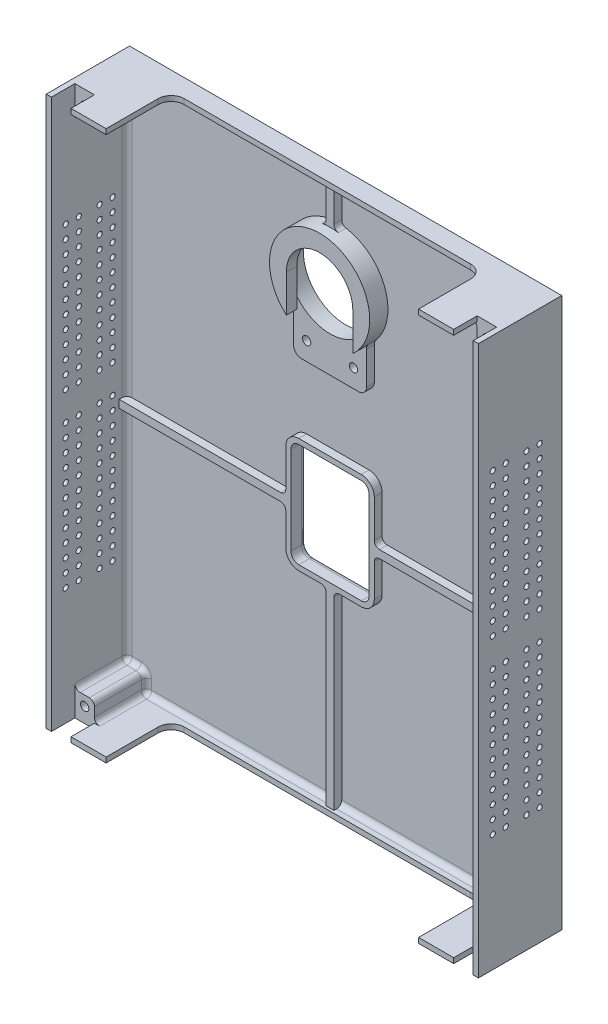
SolidWorks part; units mm, degrees
ref_plane "Front Plane" through (0, 0, 0) normal (0, 0, 1) x (1, 0, 0)
ref_plane "Top Plane" through (0, 0, 0) normal (0, 1, 0) x (1, 0, 0)
ref_plane "Right Plane" through (0, 0, 0) normal (1, 0, 0) x (0, 0, -1)
ref_plane "Plane1" through (0, 0, -1) normal (0, 0, 1) x (1, 0, 0)
sketch "Sketch5" plane through (0, 0, -1) normal (0, 0, 1) x (1, 0, 0)
  line L0 (100, 83.2573) -> (100, -169.2647) construction
  line L2 (17, 83.2573) -> (17, -127.7573)
  line L3 (17, -127.7573) -> (183, -127.7573)
  line L4 (183, 83.2573) -> (183, -127.7573)
  line L5 (17, 83.2573) -> (183, 83.2573)
  circle A0 centre (100, 48.2573) radius 16.25
  point P17 (45, 83.2573)
  dimension "D1" = 166
  dimension "D2" = 83
extrude "Boss-Extrude5" add sketch "Sketch5" along normal blind 3
sketch "Sketch6" plane through (0, 0, 2) normal (0, 0, 1) x (1, 0, 0)
  line L0 (116.25, 48.2573) -> (83.75, 48.2573) construction
  line L2 (86, 35.0451) -> (86, 18.2573)
  line L3 (86, 18.2573) -> (114, 18.2573)
  line L4 (114, 35.0451) -> (114, 18.2573)
  line L5 (100, 48.2573) -> (100, 52.872) construction
  circle A1 centre (100, 48.2573) radius 16.25
  arc A2 (114, 35.0451) -> (86, 35.0451) centre (100, 48.2573) ccw
  circle A6 centre (100, 48.2573) radius 16.25 construction
extrude "Boss-Extrude6" add sketch "Sketch6" along normal blind 3
sketch "Sketch7" plane through (0, 0, 5) normal (0, 0, 1) x (1, 0, 0)
  line L0 (112.75, 33.8351) -> (112.75, 48.2573)
  line L2 (87.25, 48.2573) -> (87.25, 33.8351)
  line L3 (100, 64.5073) -> (100, 48.2573) construction
  line L4 (100, 48.2573) -> (116.25, 48.2573) construction
  arc A8 (112.75, 33.8351) -> (87.25, 33.8351) centre (100, 48.2573) ccw
  circle A9 centre (100, 48.2573) radius 19.25 construction
  circle A10 centre (100, 48.2573) radius 16.25 construction
  circle A12 centre (100, 48.2573) radius 12.75
  arc A13 (112.75, 48.2573) -> (87.25, 48.2573) centre (100, 48.2573) ccw
  dimension "D1" = 1
extrude "Boss-Extrude7" add sketch "Sketch7" along normal blind 4
sketch "Sketch8" plane through (0, 0, 2) normal (0, 0, 1) x (1, 0, 0)
  line L4 (17, -127.7573) -> (183, -127.7573)
  line L5 (183, -127.7573) -> (183, 83.2573)
  line L6 (183, 83.2573) -> (17, 83.2573)
  line L7 (17, 83.2573) -> (17, -127.7573)
  line L8 (17, -127.7573) -> (183, -127.7573)
  line L9 (183, -127.7573) -> (183, 83.2573)
  line L10 (183, 83.2573) -> (17, 83.2573)
  line L11 (17, 83.2573) -> (17, -127.7573)
  line L12 (19, -125.7573) -> (181, -125.7573)
  line L13 (181, -125.7573) -> (181, 81.2573)
  line L14 (181, 81.2573) -> (19, 81.2573)
  line L15 (19, 81.2573) -> (19, -125.7573)
  dimension "D1" = 0
  dimension "D2" = 2
extrude "Boss-Extrude8" add sketch "Sketch8" along normal blind 29
fillet "Fillet2" radius 3 4 edges at (114, 18.2573, 3.5) (114, 35.0451, 3.5) (86, 18.2573, 3.5) (86, 35.0451, 3.5)
sketch "Sketch9" plane through (0, 0, 5) normal (0, 0, 1) x (1, 0, 0)
  line L0 (100, 48.2573) -> (100, 25.2573) construction
  line L1 (91, 25.2573) -> (109, 25.2573) construction
  line L2 (100, 25.2573) -> (100, 23.2329) construction
  circle A0 centre (91, 25.2573) radius 1.6
  circle A1 centre (109, 25.2573) radius 1.6
extrude "Cut-Extrude1" cut sketch "Sketch9" against normal up to surface (6 mm away) up to face at (100, -22.25, -1)
sketch "Sketch12" plane through (183, 0, 0) normal (1, 0, 0) x (0, 0, -1)
  circle A0 centre (-12.5, -16.7427) radius 1
  circle A1 centre (-7.5, -16.7427) radius 1
  circle A2 centre (-7.5, -11.7427) radius 1
  circle A3 centre (-7.5, -6.7427) radius 1
  circle A4 centre (-7.5, -1.7427) radius 1
  circle A5 centre (-7.5, 3.2573) radius 1
  circle A6 centre (-7.5, 8.2573) radius 1
  circle A7 centre (-7.5, 13.2573) radius 1
  circle A8 centre (-7.5, 18.2573) radius 1
  circle A9 centre (-7.5, 23.2573) radius 1
  circle A10 centre (-7.5, 28.2573) radius 1
  circle A11 centre (-7.5, 33.2573) radius 1
  circle A12 centre (-7.5, 38.2573) radius 1
  circle A13 centre (-12.5, -11.7427) radius 1
  circle A14 centre (-12.5, -6.7427) radius 1
  circle A15 centre (-12.5, -1.7427) radius 1
  circle A16 centre (-12.5, 3.2573) radius 1
  circle A17 centre (-12.5, 8.2573) radius 1
  circle A18 centre (-12.5, 13.2573) radius 1
  circle A19 centre (-12.5, 18.2573) radius 1
  circle A20 centre (-12.5, 23.2573) radius 1
  circle A21 centre (-12.5, 28.2573) radius 1
  circle A22 centre (-12.5, 33.2573) radius 1
  circle A23 centre (-12.5, 38.2573) radius 1
  circle A24 centre (-12.5, -82.7573) radius 1
  circle A25 centre (-12.5, -77.7573) radius 1
  circle A26 centre (-12.5, -72.7573) radius 1
  circle A27 centre (-12.5, -67.7573) radius 1
  circle A28 centre (-12.5, -62.7573) radius 1
  circle A29 centre (-12.5, -57.7573) radius 1
  circle A30 centre (-12.5, -52.7573) radius 1
  circle A31 centre (-12.5, -47.7573) radius 1
  circle A32 centre (-12.5, -42.7573) radius 1
  circle A33 centre (-12.5, -37.7573) radius 1
  circle A34 centre (-12.5, -32.7573) radius 1
  circle A35 centre (-7.5, -82.7573) radius 1
  circle A36 centre (-7.5, -77.7573) radius 1
  circle A37 centre (-7.5, -72.7573) radius 1
  circle A38 centre (-7.5, -67.7573) radius 1
  circle A39 centre (-7.5, -62.7573) radius 1
  circle A40 centre (-7.5, -57.7573) radius 1
  circle A41 centre (-7.5, -52.7573) radius 1
  circle A42 centre (-7.5, -47.7573) radius 1
  circle A43 centre (-7.5, -42.7573) radius 1
  circle A44 centre (-7.5, -37.7573) radius 1
  circle A45 centre (-7.5, -32.7573) radius 1
  circle A46 centre (-7.5, -27.7573) radius 1
  circle A47 centre (-12.5, -27.7573) radius 1
  circle A48 centre (-20.5, -27.7573) radius 1
  circle A49 centre (-25.5, -27.7573) radius 1
  circle A50 centre (-25.5, -32.7573) radius 1
  circle A51 centre (-25.5, -37.7573) radius 1
  circle A52 centre (-25.5, -42.7573) radius 1
  circle A53 centre (-25.5, -47.7573) radius 1
  circle A54 centre (-25.5, -52.7573) radius 1
  circle A55 centre (-25.5, -57.7573) radius 1
  circle A56 centre (-25.5, -62.7573) radius 1
  circle A57 centre (-25.5, -67.7573) radius 1
  circle A58 centre (-25.5, -72.7573) radius 1
  circle A59 centre (-25.5, -77.7573) radius 1
  circle A60 centre (-25.5, -82.7573) radius 1
  circle A61 centre (-20.5, -32.7573) radius 1
  circle A62 centre (-20.5, -37.7573) radius 1
  circle A63 centre (-20.5, -42.7573) radius 1
  circle A64 centre (-20.5, -47.7573) radius 1
  circle A65 centre (-20.5, -52.7573) radius 1
  circle A66 centre (-20.5, -57.7573) radius 1
  circle A67 centre (-20.5, -62.7573) radius 1
  circle A68 centre (-20.5, -67.7573) radius 1
  circle A69 centre (-20.5, -72.7573) radius 1
  circle A70 centre (-20.5, -77.7573) radius 1
  circle A71 centre (-20.5, -82.7573) radius 1
  circle A72 centre (-20.5, 38.2573) radius 1
  circle A73 centre (-20.5, 33.2573) radius 1
  circle A74 centre (-20.5, 28.2573) radius 1
  circle A75 centre (-20.5, 23.2573) radius 1
  circle A76 centre (-20.5, 18.2573) radius 1
  circle A77 centre (-20.5, 13.2573) radius 1
  circle A78 centre (-20.5, 8.2573) radius 1
  circle A79 centre (-20.5, 3.2573) radius 1
  circle A80 centre (-20.5, -1.7427) radius 1
  circle A81 centre (-20.5, -6.7427) radius 1
  circle A82 centre (-20.5, -11.7427) radius 1
  circle A83 centre (-25.5, 38.2573) radius 1
  circle A84 centre (-25.5, 33.2573) radius 1
  circle A85 centre (-25.5, 28.2573) radius 1
  circle A86 centre (-25.5, 23.2573) radius 1
  circle A87 centre (-25.5, 18.2573) radius 1
  circle A88 centre (-25.5, 13.2573) radius 1
  circle A89 centre (-25.5, 8.2573) radius 1
  circle A90 centre (-25.5, 3.2573) radius 1
  circle A91 centre (-25.5, -1.7427) radius 1
  circle A92 centre (-25.5, -6.7427) radius 1
  circle A93 centre (-25.5, -11.7427) radius 1
  circle A94 centre (-25.5, -16.7427) radius 1
  circle A95 centre (-20.5, -16.7427) radius 1
  dimension "D1" = 2
  dimension "D2" = 12
extrude "Cut-Extrude4" cut sketch "Sketch12" against normal up to surface (2 mm away) up to face at (181, -22.25, 16.5)
sketch "Sketch13" plane through (0, 0, -1) normal (0, 0, -1) x (-1, 0, 0)
  line L0 (-183, -30.7808) -> (-100, -30.7808) construction
  line L1 (-183, -127.7573) -> (-183, 83.2573) construction
  line L6 (-100, 83.2573) -> (-100, -30.7808) construction
  line L7 (-183, 83.2573) -> (-17, 83.2573) construction
  line L14 (-85, -47.7808) -> (-85, -13.7808)
  line L15 (-88, -10.7808) -> (-112, -10.7808)
  line L16 (-115, -13.7808) -> (-115, -47.7808)
  line L17 (-112, -50.7808) -> (-88, -50.7808)
  circle A1 centre (-100, -30.7808) radius 9 construction
  arc A15 (-88, -50.7808) -> (-85, -47.7808) centre (-88, -47.7808) ccw
  arc A16 (-85, -13.7808) -> (-88, -10.7808) centre (-88, -13.7808) ccw
  arc A17 (-112, -10.7808) -> (-115, -13.7808) centre (-112, -13.7808) ccw
  arc A18 (-115, -47.7808) -> (-112, -50.7808) centre (-112, -47.7808) ccw
extrude "Cut-Extrude5" cut sketch "Sketch13" against normal blind 3
sketch "Sketch14" plane through (17, 0, 0) normal (-1, 0, 0) x (0, 0, 1)
  circle A1 centre (12.5, -82.7573) radius 1
  circle A2 centre (12.5, -82.7573) radius 1
  circle A3 centre (12.5, -16.7427) radius 1
  circle A4 centre (12.5, -16.7427) radius 1
  circle A5 centre (7.5, 18.2573) radius 1
  circle A6 centre (7.5, 18.2573) radius 1
  circle A7 centre (7.5, 13.2573) radius 1
  circle A8 centre (7.5, 13.2573) radius 1
  circle A9 centre (7.5, 8.2573) radius 1
  circle A10 centre (7.5, 8.2573) radius 1
  circle A11 centre (7.5, 3.2573) radius 1
  circle A12 centre (7.5, 3.2573) radius 1
  circle A13 centre (7.5, -1.7427) radius 1
  circle A14 centre (7.5, -1.7427) radius 1
  circle A15 centre (7.5, -6.7427) radius 1
  circle A16 centre (7.5, -6.7427) radius 1
  circle A17 centre (7.5, -11.7427) radius 1
  circle A18 centre (7.5, -11.7427) radius 1
  circle A19 centre (7.5, -16.7427) radius 1
  circle A20 centre (7.5, -16.7427) radius 1
  circle A21 centre (12.5, 3.2573) radius 1
  circle A22 centre (12.5, 3.2573) radius 1
  circle A23 centre (12.5, -1.7427) radius 1
  circle A24 centre (12.5, -1.7427) radius 1
  circle A25 centre (12.5, -6.7427) radius 1
  circle A26 centre (12.5, -6.7427) radius 1
  circle A27 centre (12.5, -11.7427) radius 1
  circle A28 centre (12.5, -11.7427) radius 1
  circle A29 centre (7.5, 38.2573) radius 1
  circle A30 centre (7.5, 38.2573) radius 1
  circle A31 centre (7.5, 33.2573) radius 1
  circle A32 centre (7.5, 33.2573) radius 1
  circle A33 centre (7.5, 28.2573) radius 1
  circle A34 centre (7.5, 28.2573) radius 1
  circle A35 centre (7.5, 23.2573) radius 1
  circle A36 centre (7.5, 23.2573) radius 1
  circle A37 centre (12.5, -77.7573) radius 1
  circle A38 centre (12.5, -77.7573) radius 1
  circle A39 centre (12.5, 38.2573) radius 1
  circle A40 centre (12.5, 38.2573) radius 1
  circle A41 centre (12.5, 33.2573) radius 1
  circle A42 centre (12.5, 33.2573) radius 1
  circle A43 centre (12.5, 28.2573) radius 1
  circle A44 centre (12.5, 28.2573) radius 1
  circle A45 centre (12.5, 23.2573) radius 1
  circle A46 centre (12.5, 23.2573) radius 1
  circle A47 centre (12.5, 18.2573) radius 1
  circle A48 centre (12.5, 18.2573) radius 1
  circle A49 centre (12.5, 13.2573) radius 1
  circle A50 centre (12.5, 13.2573) radius 1
  circle A51 centre (12.5, 8.2573) radius 1
  circle A52 centre (12.5, 8.2573) radius 1
  circle A53 centre (12.5, -37.7573) radius 1
  circle A54 centre (12.5, -37.7573) radius 1
  circle A55 centre (12.5, -42.7573) radius 1
  circle A56 centre (12.5, -42.7573) radius 1
  circle A57 centre (12.5, -47.7573) radius 1
  circle A58 centre (12.5, -47.7573) radius 1
  circle A59 centre (12.5, -52.7573) radius 1
  circle A60 centre (12.5, -52.7573) radius 1
  circle A61 centre (12.5, -57.7573) radius 1
  circle A62 centre (12.5, -57.7573) radius 1
  circle A63 centre (12.5, -62.7573) radius 1
  circle A64 centre (12.5, -62.7573) radius 1
  circle A65 centre (12.5, -67.7573) radius 1
  circle A66 centre (12.5, -67.7573) radius 1
  circle A67 centre (12.5, -72.7573) radius 1
  circle A68 centre (12.5, -72.7573) radius 1
  circle A69 centre (7.5, -52.7573) radius 1
  circle A70 centre (7.5, -52.7573) radius 1
  circle A71 centre (7.5, -57.7573) radius 1
  circle A72 centre (7.5, -57.7573) radius 1
  circle A73 centre (7.5, -62.7573) radius 1
  circle A74 centre (7.5, -62.7573) radius 1
  circle A75 centre (7.5, -67.7573) radius 1
  circle A76 centre (7.5, -67.7573) radius 1
  circle A77 centre (7.5, -72.7573) radius 1
  circle A78 centre (7.5, -72.7573) radius 1
  circle A79 centre (7.5, -77.7573) radius 1
  circle A80 centre (7.5, -77.7573) radius 1
  circle A81 centre (7.5, -82.7573) radius 1
  circle A82 centre (7.5, -82.7573) radius 1
  circle A83 centre (12.5, -32.7573) radius 1
  circle A84 centre (12.5, -32.7573) radius 1
  circle A85 centre (25.5, -27.7573) radius 1
  circle A86 centre (25.5, -27.7573) radius 1
  circle A87 centre (20.5, -27.7573) radius 1
  circle A88 centre (20.5, -27.7573) radius 1
  circle A89 centre (12.5, -27.7573) radius 1
  circle A90 centre (12.5, -27.7573) radius 1
  circle A91 centre (7.5, -27.7573) radius 1
  circle A92 centre (7.5, -27.7573) radius 1
  circle A93 centre (7.5, -32.7573) radius 1
  circle A94 centre (7.5, -32.7573) radius 1
  circle A95 centre (7.5, -37.7573) radius 1
  circle A96 centre (7.5, -37.7573) radius 1
  circle A97 centre (7.5, -42.7573) radius 1
  circle A98 centre (7.5, -42.7573) radius 1
  circle A99 centre (7.5, -47.7573) radius 1
  circle A100 centre (7.5, -47.7573) radius 1
  circle A101 centre (25.5, -67.7573) radius 1
  circle A102 centre (25.5, -67.7573) radius 1
  circle A103 centre (25.5, -62.7573) radius 1
  circle A104 centre (25.5, -62.7573) radius 1
  circle A105 centre (25.5, -57.7573) radius 1
  circle A106 centre (25.5, -57.7573) radius 1
  circle A107 centre (25.5, -52.7573) radius 1
  circle A108 centre (25.5, -52.7573) radius 1
  circle A109 centre (25.5, -47.7573) radius 1
  circle A110 centre (25.5, -47.7573) radius 1
  circle A111 centre (25.5, -42.7573) radius 1
  circle A112 centre (25.5, -42.7573) radius 1
  circle A113 centre (25.5, -37.7573) radius 1
  circle A114 centre (25.5, -37.7573) radius 1
  circle A115 centre (25.5, -32.7573) radius 1
  circle A116 centre (25.5, -32.7573) radius 1
  circle A117 centre (20.5, -52.7573) radius 1
  circle A118 centre (20.5, -52.7573) radius 1
  circle A119 centre (20.5, -47.7573) radius 1
  circle A120 centre (20.5, -47.7573) radius 1
  circle A121 centre (20.5, -42.7573) radius 1
  circle A122 centre (20.5, -42.7573) radius 1
  circle A123 centre (20.5, -37.7573) radius 1
  circle A124 centre (20.5, -37.7573) radius 1
  circle A125 centre (20.5, -32.7573) radius 1
  circle A126 centre (20.5, -32.7573) radius 1
  circle A127 centre (25.5, -82.7573) radius 1
  circle A128 centre (25.5, -82.7573) radius 1
  circle A129 centre (25.5, -77.7573) radius 1
  circle A130 centre (25.5, -77.7573) radius 1
  circle A131 centre (25.5, -72.7573) radius 1
  circle A132 centre (25.5, -72.7573) radius 1
  circle A133 centre (20.5, 33.2573) radius 1
  circle A134 centre (20.5, 33.2573) radius 1
  circle A135 centre (20.5, 38.2573) radius 1
  circle A136 centre (20.5, 38.2573) radius 1
  circle A137 centre (20.5, -82.7573) radius 1
  circle A138 centre (20.5, -82.7573) radius 1
  circle A139 centre (20.5, -77.7573) radius 1
  circle A140 centre (20.5, -77.7573) radius 1
  circle A141 centre (20.5, -72.7573) radius 1
  circle A142 centre (20.5, -72.7573) radius 1
  circle A143 centre (20.5, -67.7573) radius 1
  circle A144 centre (20.5, -67.7573) radius 1
  circle A145 centre (20.5, -62.7573) radius 1
  circle A146 centre (20.5, -62.7573) radius 1
  circle A147 centre (20.5, -57.7573) radius 1
  circle A148 centre (20.5, -57.7573) radius 1
  circle A149 centre (20.5, -6.7427) radius 1
  circle A150 centre (20.5, -6.7427) radius 1
  circle A151 centre (20.5, -1.7427) radius 1
  circle A152 centre (20.5, -1.7427) radius 1
  circle A153 centre (20.5, 3.2573) radius 1
  circle A154 centre (20.5, 3.2573) radius 1
  circle A155 centre (20.5, 8.2573) radius 1
  circle A156 centre (20.5, 8.2573) radius 1
  circle A157 centre (20.5, 13.2573) radius 1
  circle A158 centre (20.5, 13.2573) radius 1
  circle A159 centre (20.5, 18.2573) radius 1
  circle A160 centre (20.5, 18.2573) radius 1
  circle A161 centre (20.5, 23.2573) radius 1
  circle A162 centre (20.5, 23.2573) radius 1
  circle A163 centre (20.5, 28.2573) radius 1
  circle A164 centre (20.5, 28.2573) radius 1
  circle A165 centre (25.5, 8.2573) radius 1
  circle A166 centre (25.5, 8.2573) radius 1
  circle A167 centre (25.5, 13.2573) radius 1
  circle A168 centre (25.5, 13.2573) radius 1
  circle A169 centre (25.5, 18.2573) radius 1
  circle A170 centre (25.5, 18.2573) radius 1
  circle A171 centre (25.5, 23.2573) radius 1
  circle A172 centre (25.5, 23.2573) radius 1
  circle A173 centre (25.5, 28.2573) radius 1
  circle A174 centre (25.5, 28.2573) radius 1
  circle A175 centre (25.5, 33.2573) radius 1
  circle A176 centre (25.5, 33.2573) radius 1
  circle A177 centre (25.5, 38.2573) radius 1
  circle A178 centre (25.5, 38.2573) radius 1
  circle A179 centre (20.5, -11.7427) radius 1
  circle A180 centre (20.5, -11.7427) radius 1
  circle A181 centre (20.5, -16.7427) radius 1
  circle A182 centre (20.5, -16.7427) radius 1
  circle A183 centre (25.5, -16.7427) radius 1
  circle A184 centre (25.5, -16.7427) radius 1
  circle A185 centre (25.5, -11.7427) radius 1
  circle A186 centre (25.5, -11.7427) radius 1
  circle A187 centre (25.5, -6.7427) radius 1
  circle A188 centre (25.5, -6.7427) radius 1
  circle A189 centre (25.5, -1.7427) radius 1
  circle A190 centre (25.5, -1.7427) radius 1
  circle A191 centre (25.5, 3.2573) radius 1
  circle A192 centre (25.5, 3.2573) radius 1
  dimension "D1" = 0
  dimension "D2" = 0
  dimension "D3" = 0
  dimension "D4" = 0
  dimension "D5" = 0
  dimension "D6" = 0
  dimension "D7" = 0
  dimension "D8" = 0
  dimension "D9" = 0
  dimension "D10" = 0
  dimension "D11" = 0
  dimension "D12" = 0
  dimension "D13" = 0
  dimension "D14" = 0
  dimension "D15" = 0
  dimension "D16" = 0
  dimension "D17" = 0
  dimension "D18" = 0
  dimension "D19" = 0
  dimension "D20" = 0
  dimension "D21" = 0
  dimension "D22" = 0
  dimension "D23" = 0
  dimension "D24" = 0
  dimension "D25" = 0
  dimension "D26" = 0
  dimension "D27" = 0
  dimension "D28" = 0
  dimension "D29" = 0
  dimension "D30" = 0
  dimension "D31" = 0
  dimension "D32" = 0
  dimension "D33" = 0
  dimension "D34" = 0
  dimension "D35" = 0
  dimension "D36" = 0
  dimension "D37" = 0
  dimension "D38" = 0
  dimension "D39" = 0
  dimension "D40" = 0
  dimension "D41" = 0
  dimension "D42" = 0
  dimension "D43" = 0
  dimension "D44" = 0
  dimension "D45" = 0
  dimension "D46" = 0
  dimension "D47" = 0
  dimension "D48" = 0
  dimension "D49" = 0
  dimension "D50" = 0
  dimension "D51" = 0
  dimension "D52" = 0
  dimension "D53" = 0
  dimension "D54" = 0
  dimension "D55" = 0
  dimension "D56" = 0
  dimension "D57" = 0
  dimension "D58" = 0
  dimension "D59" = 0
  dimension "D60" = 0
  dimension "D61" = 0
  dimension "D62" = 0
  dimension "D63" = 0
  dimension "D64" = 0
  dimension "D65" = 0
  dimension "D66" = 0
  dimension "D67" = 0
  dimension "D68" = 0
  dimension "D69" = 0
  dimension "D70" = 0
  dimension "D71" = 0
  dimension "D72" = 0
  dimension "D73" = 0
  dimension "D74" = 0
  dimension "D75" = 0
  dimension "D76" = 0
  dimension "D77" = 0
  dimension "D78" = 0
  dimension "D79" = 0
  dimension "D80" = 0
  dimension "D81" = 0
  dimension "D82" = 0
  dimension "D83" = 0
  dimension "D84" = 0
  dimension "D85" = 0
  dimension "D86" = 0
  dimension "D87" = 0
  dimension "D88" = 0
  dimension "D89" = 0
  dimension "D90" = 0
  dimension "D91" = 0
  dimension "D92" = 0
  dimension "D93" = 0
  dimension "D94" = 0
  dimension "D95" = 0
  dimension "D96" = 0
extrude "Cut-Extrude6" cut sketch "Sketch14" against normal up to surface (2 mm away) up to face at (19, -22.25, 16.5)
sketch "Sketch15" plane through (0, -127.7573, 0) normal (0, -1, 0) x (1, 0, 0)
  line L5 (100, -1) -> (100, 31) construction
  line L6 (17, -1) -> (183, -1) construction
  line L7 (17, 31) -> (183, 31) construction
  line L8 (40, 31) -> (160, 31)
  line L9 (40, 31) -> (40, 11)
  line L10 (45, 6) -> (155, 6)
  line L11 (160, 31) -> (160, 11)
  arc A4 (155, 6) -> (160, 11) centre (155, 11) ccw
  arc A5 (40, 11) -> (45, 6) centre (45, 11) ccw
  point P12 (160, 6)
  point P15 (40, 6)
  dimension "D4" = 5
  dimension "D1" = 60
  dimension "D2" = 120
  dimension "D3" = 25
extrude "Cut-Extrude7" cut sketch "Sketch15" against normal up to surface (2 mm away) up to face at (100, -125.7573, 16.5)
sketch "Sketch16" plane through (0, 83.2573, 0) normal (0, 1, 0) x (1, 0, 0)
  line L4 (40, -31) -> (160, -31)
  line L5 (40, -31) -> (160, -31)
  line L6 (160, -31) -> (160, -11)
  line L7 (160, -31) -> (160, -11)
  line L12 (155, -6) -> (45, -6)
  line L13 (155, -6) -> (45, -6)
  line L14 (40, -11) -> (40, -31)
  line L15 (40, -11) -> (40, -31)
  arc A2 (160, -11) -> (155, -6) centre (155, -11) ccw
  arc A3 (160, -11) -> (155, -6) centre (155, -11) ccw
  arc A4 (45, -6) -> (40, -11) centre (45, -11) ccw
  arc A5 (45, -6) -> (40, -11) centre (45, -11) ccw
  dimension "D1" = 0
extrude "Cut-Extrude8" cut sketch "Sketch16" against normal up to surface (2 mm away) up to face at (100, 81.2573, 16.5)
sketch "Sketch18" plane through (0, 0, 2) normal (0, 0, 1) x (1, 0, 0)
  line L1 (19, -125.7573) -> (26.5, -125.7573)
  line L2 (19, -125.7573) -> (19, -118.2573)
  line L3 (19, -118.2573) -> (26.5, -118.2573)
  line L4 (26.5, -125.7573) -> (26.5, -118.2573)
  line L5 (181, -125.7573) -> (173.5, -125.7573)
  line L6 (181, -125.7573) -> (181, -118.2573)
  line L7 (181, -118.2573) -> (173.5, -118.2573)
  line L8 (173.5, -125.7573) -> (173.5, -118.2573)
  line L9 (19, 81.2573) -> (26.5, 81.2573)
  line L10 (19, 81.2573) -> (19, 73.7573)
  line L11 (19, 73.7573) -> (26.5, 73.7573)
  line L12 (26.5, 81.2573) -> (26.5, 73.7573)
  line L13 (181, 81.2573) -> (173.5, 81.2573)
  line L14 (181, 81.2573) -> (181, 73.7573)
  line L15 (181, 73.7573) -> (173.5, 73.7573)
  line L16 (173.5, 81.2573) -> (173.5, 73.7573)
extrude "Boss-Extrude10" add sketch "Sketch18" along normal blind 20
fillet "Fillet3" radius 2 12 edges at (181, 73.7573, 12) (173.5, 73.7573, 12) (173.5, 81.2573, 12) (26.5, 81.2573, 12) (26.5, 73.7573, 12) (19, 73.7573, 12) (19, -118.2573, 12) (26.5, -118.2573, 12) (26.5, -125.7573, 12) (181, -118.2573, 12) (173.5, -118.2573, 12) (173.5, -125.7573, 12)
sketch "Sketch19" plane through (0, 0, 22) normal (0, 0, 1) x (1, 0, 0)
  line L4 (100, -127.7573) -> (100, 83.2573) construction
  line L5 (45, -127.7573) -> (155, -127.7573) construction
  line L6 (155, 83.2573) -> (45, 83.2573) construction
  line L7 (100, -22.25) -> (17, -22.25) construction
  line L8 (17, 83.2573) -> (17, -127.7573) construction
  circle A0 centre (22.75, -122.0073) radius 1.6
  circle A1 centre (177.25, -122.0073) radius 1.6
  circle A2 centre (177.25, 77.5073) radius 1.6
  circle A3 centre (22.75, 77.5073) radius 1.6
extrude "Cut-Extrude9" cut sketch "Sketch19" against normal up to surface (23 mm away) up to face at (100, -30.7808, -1)
fillet "Fillet4" radius 2 24 edges at (180.4142, -117.6715, 2) (177.25, -118.2573, 2) (174.0858, -118.8431, 2) (173.5, -122.0073, 2) (172.9142, -125.1715, 2) (100, -125.7573, 2) (27.0858, -125.1715, 2) (26.5, -122.0073, 2) (25.9142, -118.8431, 2) (22.75, -118.2573, 2) (19.5858, -117.6715, 2) (19, -22.25, 2) (19.5858, 73.1715, 2) (22.75, 73.7573, 2) (25.9142, 74.3431, 2) (26.5, 77.5073, 2) (27.0858, 80.6715, 2) (100, 81.2573, 2) (172.9142, 80.6715, 2) (173.5, 77.5073, 2) (174.0858, 74.3431, 2) (177.25, 73.7573, 2) (180.4142, 73.1715, 2) (181, -22.25, 2)
sketch "Sketch20" plane through (0, 0, 2) normal (0, 0, 1) x (1, 0, 0)
  line L0 (83, -30.2573) -> (83, -13.7808)
  line L1 (155, 83.2573) -> (45, 83.2573) construction
  line L2 (45, -127.7573) -> (155, -127.7573) construction
  line L3 (88, -10.7808) -> (112, -10.7808) construction
  line L4 (101.5, -127.7573) -> (98.5, -127.7573)
  line L5 (101.5, -127.7573) -> (101.5, -52.7808)
  line L6 (101.5, 83.2573) -> (98.5, 83.2573)
  line L7 (98.5, -127.7573) -> (98.5, -52.7808)
  line L8 (115, -13.7808) -> (115, -47.7808) construction
  line L9 (112, -50.7808) -> (88, -50.7808) construction
  line L10 (85, -47.7808) -> (85, -13.7808) construction
  line L11 (88, -10.7808) -> (112, -10.7808)
  line L12 (115, -13.7808) -> (115, -47.7808)
  line L13 (112, -50.7808) -> (88, -50.7808)
  line L14 (85, -47.7808) -> (85, -13.7808)
  line L15 (88, -8.7808) -> (112, -8.7808)
  line L16 (117, -13.7808) -> (117, -30.2573)
  line L17 (112, -52.7808) -> (101.5, -52.7808)
  line L18 (83, -47.7808) -> (83, -33.2573)
  line L20 (183, -127.7573) -> (183, 83.2573) construction
  line L21 (183, -33.2573) -> (117, -33.2573)
  line L22 (183, -33.2573) -> (183, -30.2573)
  line L23 (183, -30.2573) -> (117, -30.2573)
  line L24 (17, -33.2573) -> (17, -30.2573)
  line L25 (17, 83.2573) -> (17, -127.7573) construction
  line L26 (83, -33.2573) -> (17, -33.2573)
  line L28 (98.5, -52.7808) -> (88, -52.7808)
  line L31 (83, -30.2573) -> (17, -30.2573)
  line L33 (112, -52.7808) -> (88, -52.7808) construction
  line L35 (117, -33.2573) -> (117, -47.7808)
  line L38 (117, -13.7808) -> (117, -47.7808) construction
  line L39 (88, -8.7808) -> (112, -8.7808) construction
  line L40 (83, -47.7808) -> (83, -13.7808) construction
  line L44 (98.5, 64.4379) -> (98.5, 83.2573)
  line L45 (101.5, 64.4379) -> (101.5, 83.2573)
  line L49 (112.75, 48.2573) -> (112.75, 38.1826)
  line L51 (87.25, 38.1826) -> (87.25, 48.2573)
  arc A0 (88, -10.7808) -> (85, -13.7808) centre (88, -13.7808) ccw construction
  arc A1 (115, -13.7808) -> (112, -10.7808) centre (112, -13.7808) ccw construction
  arc A2 (112, -50.7808) -> (115, -47.7808) centre (112, -47.7808) ccw construction
  arc A3 (85, -47.7808) -> (88, -50.7808) centre (88, -47.7808) ccw construction
  arc A4 (88, -10.7808) -> (85, -13.7808) centre (88, -13.7808) ccw
  arc A5 (115, -13.7808) -> (112, -10.7808) centre (112, -13.7808) ccw
  arc A6 (112, -50.7808) -> (115, -47.7808) centre (112, -47.7808) ccw
  arc A7 (85, -47.7808) -> (88, -50.7808) centre (88, -47.7808) ccw
  arc A8 (117, -13.7808) -> (112, -8.7808) centre (112, -13.7808) ccw
  arc A9 (112, -52.7808) -> (117, -47.7808) centre (112, -47.7808) ccw
  arc A10 (83, -47.7808) -> (88, -52.7808) centre (88, -47.7808) ccw
  arc A11 (88, -8.7808) -> (83, -13.7808) centre (88, -13.7808) ccw
  arc A14 (112.75, 48.2573) -> (87.25, 48.2573) centre (100, 48.2573) ccw
  arc A15 (112.75, 38.1826) -> (87.25, 38.1826) centre (100, 48.2573) ccw
  arc A18 (101.5, 64.4379) -> (98.5, 64.4379) centre (100, 48.2573) ccw
  point P0 (111.5893, -8.7808)
  dimension "D1" = 0
  dimension "D3" = 2
extrude "Boss-Extrude11" add sketch "Sketch20" along normal blind 3
fillet "Fillet5" radius 2 8 edges at (98.5, -52.7808, 3.5) (101.5, -52.7808, 3.5) (117, -33.2573, 3.5) (117, -30.2573, 3.5) (83, -33.2573, 3.5) (83, -30.2573, 3.5) (101.5, 67.4488, 3.5) (98.5, 67.4488, 3.5)
sketch "Sketch21" plane through (0, 0, -1) normal (0, 0, -1) x (-1, 0, 0)
  circle A0 centre (-109, 25.2573) radius 2.25
  circle A1 centre (-91, 25.2573) radius 2.25
extrude "Cut-Extrude10" cut sketch "Sketch21" against normal blind 3
fillet "Fillet6" radius 2 8 edges at (85.8787, -49.9021, -1) (100, -50.7808, -1) (114.1213, -49.9021, -1) (115, -30.7808, -1) (114.1213, -11.6594, -1) (100, -10.7808, -1) (85.8787, -11.6594, -1) (85, -30.7808, -1)
chamfer "Chamfer1" distance 1.5 angle 45 4 edges at (21.15, 77.5073, -1) (21.15, -122.0073, -1) (175.65, -122.0073, -1) (175.65, 77.5073, -1)
sketch "Sketch22" plane through (0, 0, 31) normal (0, 0, 1) x (1, 0, 0)
  line L0 (173.5, -120.2573) -> (173.5, -123.7573) construction
  line L1 (173.5, -125.7573) -> (173.5, -127.7573)
  line L3 (181, -125.7573) -> (173.5, -125.7573)
  line L4 (160, -127.7573) -> (183, -127.7573) construction
  line L5 (183, -127.7573) -> (183, 83.2573) construction
  line L7 (181, -127.7573) -> (173.5, -127.7573)
  line L8 (100, -127.7573) -> (100, 83.2573) construction
  line L9 (45, -127.7573) -> (155, -127.7573) construction
  line L10 (155, 83.2573) -> (45, 83.2573) construction
  line L11 (183, -22.25) -> (17, -22.25) construction
  line L12 (17, 83.2573) -> (17, -127.7573) construction
  line L13 (19, -127.7573) -> (26.5, -127.7573)
  line L15 (19, -125.7573) -> (26.5, -125.7573)
  line L16 (26.5, -125.7573) -> (26.5, -127.7573)
  line L17 (26.5, 81.2573) -> (26.5, 83.2573)
  line L18 (19, 81.2573) -> (26.5, 81.2573)
  line L20 (19, 83.2573) -> (26.5, 83.2573)
  line L21 (181, 83.2573) -> (173.5, 83.2573)
  line L23 (181, 81.2573) -> (173.5, 81.2573)
  line L24 (173.5, 81.2573) -> (173.5, 83.2573)
  line L25 (19, 83.2573) -> (19, 81.2573)
  line L26 (181, 83.2573) -> (181, 81.2573)
  line L27 (181, -125.7573) -> (181, -127.7573)
  line L28 (19, -125.7573) -> (19, -127.7573)
  dimension "D1" = 2
extrude "Cut-Extrude11" cut sketch "Sketch22" against normal up to surface (9 mm away) up to face at (21.15, 77.5073, 22)
